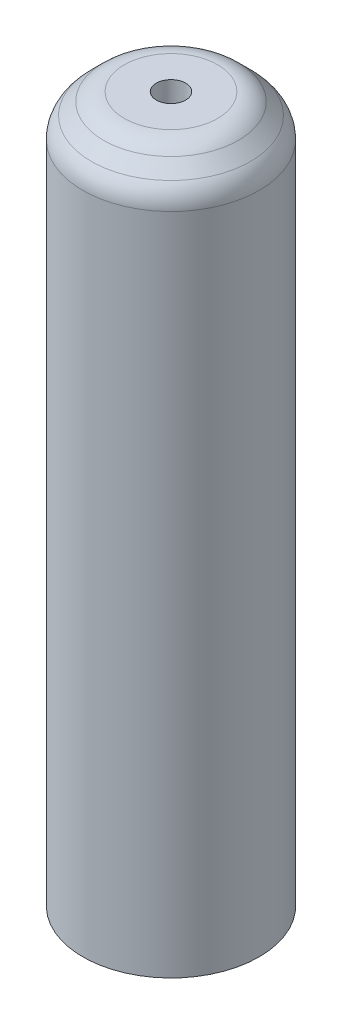
SolidWorks part; units mm, degrees
material "ABS"
ref_plane "Front Plane" through (0, 0, 0) normal (0, 0, 1) x (1, 0, 0)
ref_plane "Top Plane" through (0, 0, 0) normal (0, 1, 0) x (1, 0, 0)
ref_plane "Right Plane" through (0, 0, 0) normal (1, 0, 0) x (0, 0, -1)
sketch "Sketch1" plane through (0, 0, 0) normal (0, 0, 1) x (1, 0, 0)
  line L0 (0, -1000) -> (0, 49000) construction
  line L1 (3, 0) -> (3, 24)
  line L4 (0.5, 22) -> (1, 21.5)
  line L5 (1, 21.5) -> (1, 0)
  line L6 (1, 0) -> (3, 0)
  line L7 (0.5, 22) -> (0.5, 24)
  line L8 (0.5, 24) -> (3, 24)
  dimension "D1" = 6
  dimension "D2" = 2
  dimension "D3" = 1
  dimension "D4" = 45
  dimension "D5" = 2
  dimension "D6" = 24
revolve "Revolve1" add sketch "Sketch1" angle 360 about L0
chamfer "Chamfer1" distance 1 angle 45 1 edges at (3, 24, 0)
fillet "Fillet1" radius 1 2 edges at (-2, 24, 0) (-3, 23, 0)
